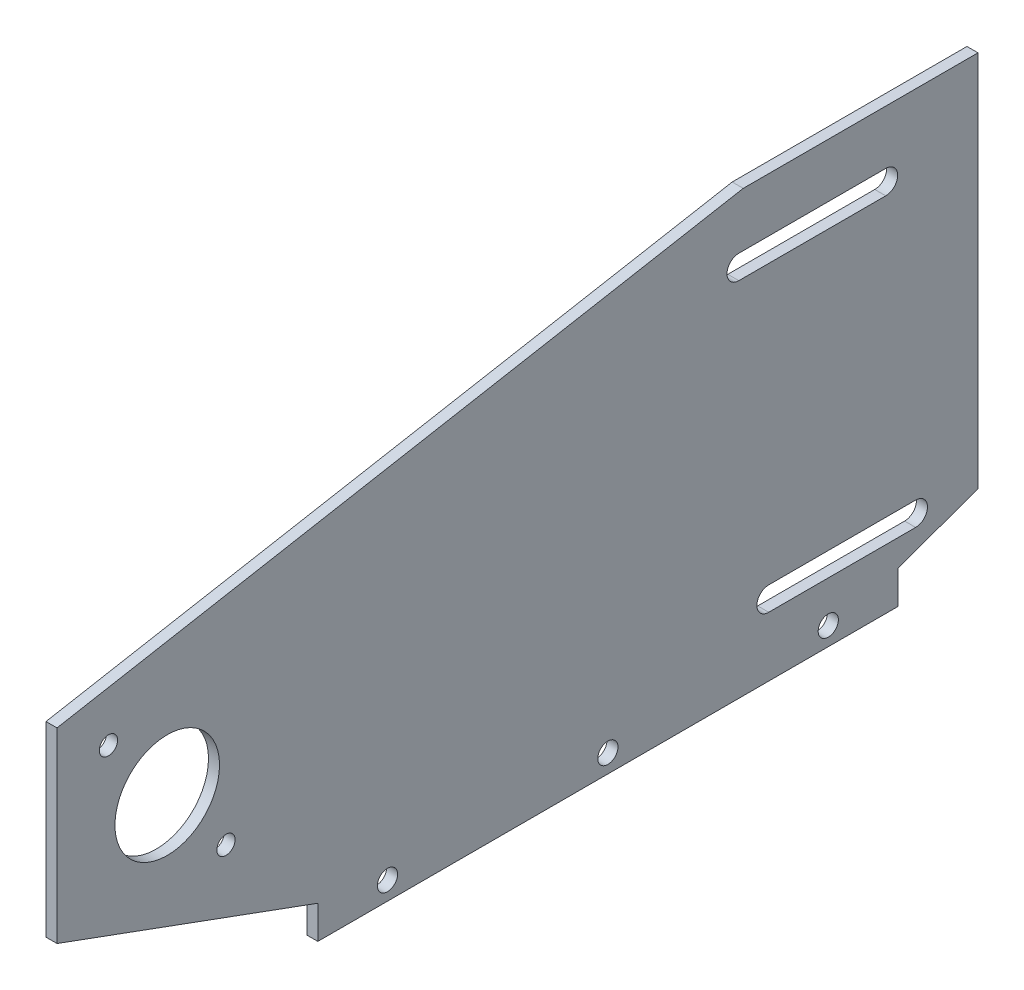
SolidWorks part; units mm, degrees
ref_plane "Front Plane" through (0, 0, 0) normal (0, 0, 1) x (1, 0, 0)
ref_plane "Top Plane" through (0, 0, 0) normal (0, 1, 0) x (1, 0, 0)
ref_plane "Right Plane" through (0, 0, 0) normal (1, 0, 0) x (0, 0, -1)
sketch "Sketch1" plane through (0, 0, 0) normal (1, 0, 0) x (0, 0, -1)
  line L1 (0, 0) -> (300, 0)
  line L2 (0, 0) -> (0, 150)
  line L3 (0, 150) -> (300, 150)
  line L4 (300, 0) -> (300, 150)
  circle A0 centre (30, 55) radius 14.235
  dimension "D1" = 300
  dimension "D5" = 28.47
  dimension "D4" = 55
  dimension "D2" = 150
  dimension "D3" = 30
extrude "Boss-Extrude1" add sketch "Sketch1" along normal blind 3
sketch "Sketch2" plane through (0, 0, 0) normal (-1, 0, 0) x (0, 0, 1)
  line L3 (-185.6114, 101.7084) -> (-225.6114, 101.7084) construction
  line L4 (-185.6114, 98.4784) -> (-225.6114, 98.4784)
  line L5 (-185.6114, 104.9384) -> (-225.6114, 104.9384)
  line L11 (-233.7436, 19.4567) -> (-193.7436, 19.4567) construction
  line L12 (-233.7436, 22.6817) -> (-193.7436, 22.6817)
  line L13 (-233.7436, 16.2317) -> (-193.7436, 16.2317)
  line L14 (0, 0) -> (-300, 0) construction
  line L15 (-300, 150) -> (0, 150) construction
  line L16 (-300, 0) -> (-300, 150) construction
  line L17 (0, 150) -> (0, 0) construction
  arc A3 (-185.6114, 98.4784) -> (-185.6114, 104.9384) centre (-185.6114, 101.7084) ccw
  arc A4 (-225.6114, 104.9384) -> (-225.6114, 98.4784) centre (-225.6114, 101.7084) ccw
  arc A9 (-233.7436, 22.6817) -> (-233.7436, 16.2317) centre (-233.7436, 19.4567) ccw
  arc A10 (-193.7436, 16.2317) -> (-193.7436, 22.6817) centre (-193.7436, 19.4567) ccw
  circle A11 centre (-290, 140) radius 3.225
  circle A12 centre (-10, 110) radius 3.225
  circle A13 centre (-290, 30) radius 3.225
  point P0 (-205.6114, 101.7084)
  point P7 (-213.7436, 10.55)
  point P9 (-205.6114, 101.7084)
  point P34 (-213.7436, 19.4567)
  dimension "D8" = 3.225
  dimension "D13" = 6.45
  dimension "D14" = 6.45
  dimension "D15" = 6.45
  dimension "D3" = 40
  dimension "D5" = 40
  dimension "D16" = 10
  dimension "D17" = 10
  dimension "D18" = 30
  dimension "D19" = 10
  dimension "D20" = 10
  dimension "D21" = 110
extrude "Cut-Extrude1" cut sketch "Sketch2" against normal up to next
sketch "Sketch3" plane through (3, 0, 0) normal (1, 0, 0) x (0, 0, -1)
  line L0 (0, 150) -> (0, 0) construction
  line L1 (0, 0) -> (300, 0) construction
  circle A1 centre (14.0057, 74.7318) radius 2.4892
  circle A2 centre (45.9943, 35.2682) radius 2.4892
  dimension "D1" = 14.0057
  dimension "D2" = 45.9943
  dimension "D3" = 74.7318
  dimension "D4" = 35.2682
extrude "Cut-Extrude2" cut sketch "Sketch3" against normal through all
sketch "Sketch4" plane through (3, 0, 0) normal (1, 0, 0) x (0, 0, -1)
  line L0 (71, 9) -> (0, 35)
  line L1 (0, 150) -> (0, 0) construction
  line L2 (0, 35) -> (0, 0)
  line L3 (0, 0) -> (71, 0)
  line L4 (0, 0) -> (300, 0) construction
  line L5 (71, 9) -> (71, 0) construction
  line L6 (71, 0) -> (71, 9)
  dimension "D1" = 35
  dimension "D2" = 71
  dimension "D3" = 9
extrude "Cut-Extrude3" cut sketch "Sketch4" against normal through all
sketch "Sketch5" plane through (3, 0, 0) normal (1, 0, 0) x (0, 0, -1)
  line L0 (228.924, 9) -> (250.718, 16.8759)
  line L4 (71, 0) -> (300, 0) construction
  line L5 (228.924, 9) -> (228.924, 0) construction
  line L6 (228.924, 0) -> (228.924, 9)
  line L7 (250.718, 16.8759) -> (250.718, 150)
  line L8 (300, 150) -> (0, 150) construction
  line L9 (250.718, 150) -> (312.6604, 150)
  line L10 (312.6604, 150) -> (312.6604, -2.8296)
  line L11 (312.6604, -2.8296) -> (228.924, 0)
extrude "Cut-Extrude4" cut sketch "Sketch5" against normal blind 10
sketch "Sketch6" plane through (3, 0, 0) normal (1, 0, 0) x (0, 0, -1)
  line L0 (0, 85.8486) -> (186.8026, 119.6415)
  line L1 (0, 150) -> (0, 35) construction
  line L4 (0, 150) -> (0, 85.8486)
  line L6 (0, 150) -> (250.718, 150)
  line L8 (186.8026, 119.6415) -> (250.718, 119.6415)
  line L9 (250.718, 150) -> (250.718, 16.8759) construction
  line L10 (250.718, 119.6415) -> (250.718, 150)
extrude "Cut-Extrude5" cut sketch "Sketch6" against normal blind 10
sketch "Sketch7" plane through (0, 0, 0) normal (-1, 0, 0) x (0, 0, 1)
  line L0 (-71, 0) -> (-228.924, 0) construction
  circle A0 centre (-209.962, 5) radius 2.75
  circle A1 centre (-149.962, 5) radius 2.75
  circle A2 centre (-89.962, 5) radius 2.75
  point P8 (-149.962, 0)
  point P9 (0, 0)
  dimension "D1" = 5.5
  dimension "D2" = 5.5
  dimension "D3" = 5.5
  dimension "D4" = 60
  dimension "D5" = 60
  dimension "D6" = 5
extrude "Cut-Extrude6" cut sketch "Sketch7" against normal through all
